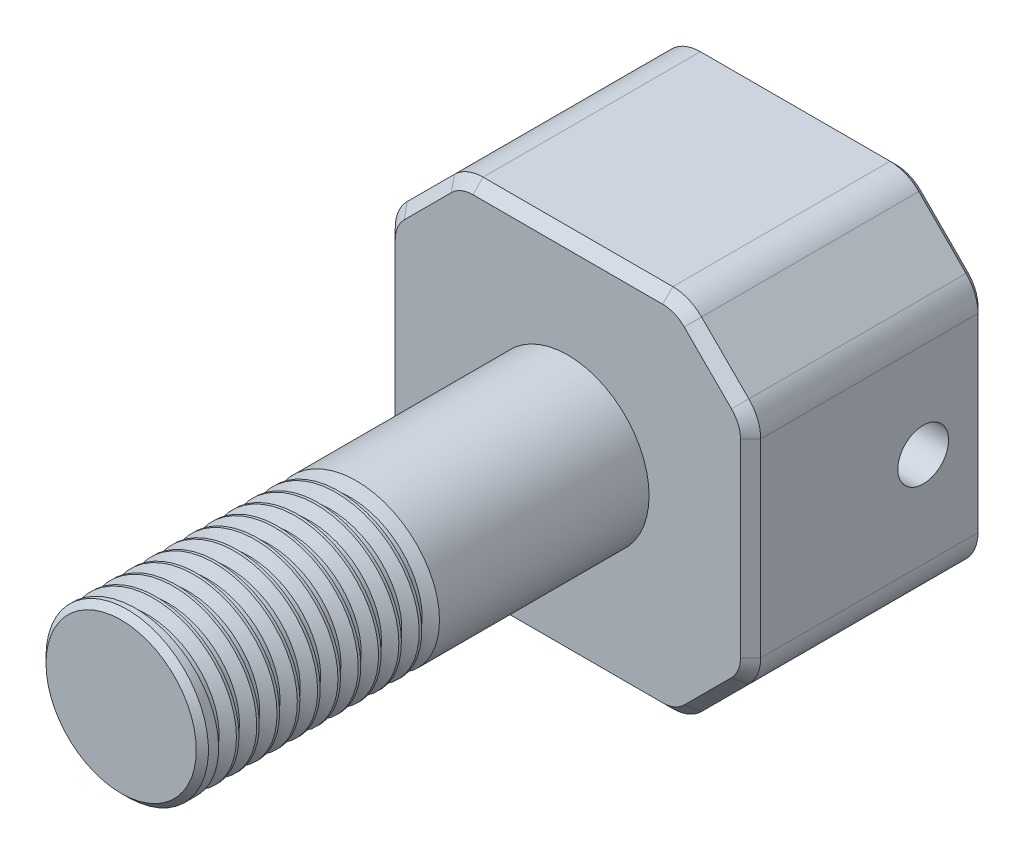
SolidWorks part; units mm, degrees
ref_plane "Front Plane" through (0, 0, 0) normal (0, 0, 1) x (1, 0, 0)
ref_plane "Top Plane" through (0, 0, 0) normal (0, 1, 0) x (1, 0, 0)
ref_plane "Right Plane" through (0, 0, 0) normal (1, 0, 0) x (0, 0, -1)
sketch "Sketch1" plane through (0, 0, 0) normal (0, 0, 1) x (1, 0, 0)
  line L1 (-9, -9) -> (9, -9)
  line L2 (-9, -9) -> (-9, 9)
  line L3 (-9, 9) -> (9, 9)
  line L4 (9, -9) -> (9, 9)
  line L5 (-9, -9) -> (9, 9) construction
  line L6 (-9, 9) -> (9, -9) construction
  point P0 (0, 0)
  dimension "D1" = 18
extrude "Boss-Extrude1" add sketch "Sketch1" along normal blind 11.5
sketch "Sketch2" plane through (0, 0, 11.5) normal (0, 0, 1) x (1, 0, 0)
  circle A0 centre (0, 0) radius 4
  dimension "D1" = 8
extrude "Boss-Extrude2" add sketch "Sketch2" along normal blind 22
sketch "Sketch3" plane through (0, 0, 0) normal (0, 0, -1) x (-1, 0, 0)
  circle A0 centre (0, 0) radius 4
  dimension "D1" = 8
extrude "Cut-Extrude1" cut sketch "Sketch3" against normal blind 9.6
sketch "Sketch4" plane through (9, 0, 0) normal (1, 0, 0) x (0, 0, -1)
  line L0 (-9.6, -4) -> (-9.6, 4) construction
  line L1 (-9.6, -4) -> (-9.6, 4)
  line L2 (-9.6, 0) -> (-3, 0) construction
  dimension "D1" = 6.6
hole_wizard "M3x0.5 Tapped Hole1" positions "3DSketch1" profile "Sketch5" tap size "M3x0.5" standard "ANSI Metric"
sketch3d "3DSketch1"
  point P0 (9, 0, 3)
sketch "Sketch5" plane through (9, 0, 3) normal (0, 1, 0) x (0, 0, -1)
  line L0 (0, 0) -> (0, 6.7511)
  line L1 (0, 6.7511) -> (1.25, 6)
  line L2 (1.25, 6) -> (1.25, 0)
  line L5 (1.25, 0) -> (0, 0)
  line L10 (0, 6.7511) -> (-1.25, 6) construction
  line L11 (0, -6.35) -> (0, 107.95) construction
  dimension "Tap Drill Dia." = 2.5
  dimension "Tap Drill Depth" = 6
  dimension "Drill Angle" = 118
cosmetic thread "Hole Thread1" parameters "D1"=3, "D2"=3
sketch "Sketch11" plane through (-9, 0, 0) normal (-1, 0, 0) x (0, 0, 1)
  line L0 (0, 9) -> (0, -9) construction
  line L1 (3, 3) -> (0, 3)
  line L3 (3, -3) -> (0, -3)
  line L4 (0, 3) -> (0, -3)
  line L5 (3, 3) -> (0, -3) construction
  line L6 (3, -3) -> (0, 3) construction
  arc A0 (3, -3) -> (3, 3) centre (3, 0) ccw
  point P0 (3, 0)
  point P9 (1.5, 0)
extrude "Cut-Extrude2" cut sketch "Sketch11" against normal blind 2
sketch "Sketch12" plane through (-7, 0, 0) normal (-1, 0, 0) x (0, 0, 1)
  circle A0 centre (3, 0) radius 1.56
  point P0 (3, 0)
  dimension "D1" = 3.12
extrude "Cut-Extrude3" cut sketch "Sketch12" against normal blind 7
chamfer "Chamfer1" distance 3.5 angle 45 4 edges at (-9, -9, 5.75) (-9, 9, 5.75) (9, 9, 5.75) (9, -9, 5.75)
fillet "Fillet1" radius 2 8 edges at (-5.5, -9, 5.75) (-9, -5.5, 5.75) (-9, 5.5, 5.75) (-5.5, 9, 5.75) (5.5, -9, 5.75) (9, -5.5, 5.75) (5.5, 9, 5.75) (9, 5.5, 5.75)
sketch "Sketch10" plane through (0, 0, 11.5) normal (0, 0, 1) x (1, 0, 0)
  circle A0 centre (0, 0) radius 4
  dimension "D1" = 8
extrude "Boss-Extrude3" add sketch "Sketch10" along normal offset from surface (11 mm away) 11 up to face at (4, 0, 33.5)
fillet "Fillet3" radius 1 2 edges at (-8, -3, 0) (-8, 3, 0)
chamfer "Chamfer2" distance 0.3 angle 45 22 edges at (0, -9, 0) (5.4369, -8.8478, 0) (-5.4369, -8.8478, 0) (7.25, -7.25, 0) (-7.25, -7.25, 0) (8.8478, -5.4369, 0) (-8.8478, -5.4369, 0) (9, 0, 0) (8.8478, 5.4369, 0) (-8.8478, 5.4369, 0) (7.25, 7.25, 0) (-7.25, 7.25, 0) (5.4369, 8.8478, 0) (-5.4369, 8.8478, 0) (0, 9, 0) (4, 0, 33.5) (-9, -4.3358, 0) (-9, -3, 2) (-9, 0, 6) (-9, 3, 2) (-9, -3.2929, 0.2929) (-9, 3.2929, 0.2929)
thread "M8螺纹" pitch 1 method cut profile "Thread Profile3" start angle 0, offset 0, length 11, pitch 1, diameter 8
ref_plane "Plane3" through (-4, 0, 33.2) normal (0, -1, 0) x (-1, 0, 0)
sketch "Thread Profile3" plane through (-4, 0, 33.2) normal (0, -1, 0) x (-1, 0, 0)
  line L0 (0, 0) -> (0, 1) construction
  line L11 (0, 0) -> (0, 0.875)
  line L12 (0, 0.875) -> (-0.5413, 0.5625)
  line L13 (-0.5413, 0.5625) -> (-0.5413, 0.3125)
  line L15 (-0.5413, 0.3125) -> (0, 0)
  line L17 (-0.5413, 0.4375) -> (0, 0.4375) construction
  point P2 (0, 0)
  dimension "Pitch" = 1
  dimension "Profile_Angle" = 60
  dimension "Profile_Land" = 0.25
  dimension "Profile_Height" = 0.5413
sketch "Sketch13" plane through (0, 0, 0) normal (0, 0, -1) x (-1, 0, 0)
  circle A0 centre (0, 0) radius 7
  circle A1 centre (0, 0) radius 4 construction
  circle A2 centre (0, 0) radius 4
  dimension "D1" = 14
extrude "Boss-Extrude4" add sketch "Sketch13" along normal blind 1.6
chamfer "Chamfer3" distance 0.2 angle 45 2 edges at (-4, 0, -1.6) (-7, 0, -1.6)
chamfer "Chamfer4" distance 0.5 angle 45 16 edges at (7.25, 7.25, 11.5) (5.4369, 8.8478, 11.5) (8.8478, 5.4369, 11.5) (0, 9, 11.5) (9, 0, 11.5) (-5.4369, 8.8478, 11.5) (8.8478, -5.4369, 11.5) (-7.25, 7.25, 11.5) (7.25, -7.25, 11.5) (-8.8478, 5.4369, 11.5) (5.4369, -8.8478, 11.5) (-9, 0, 11.5) (0, -9, 11.5) (-8.8478, -5.4369, 11.5) (-5.4369, -8.8478, 11.5) (-7.25, -7.25, 11.5)
other "移动面1" face at (-4, 0, 9.6) offset 0.1 parameters "D1"=0.1
